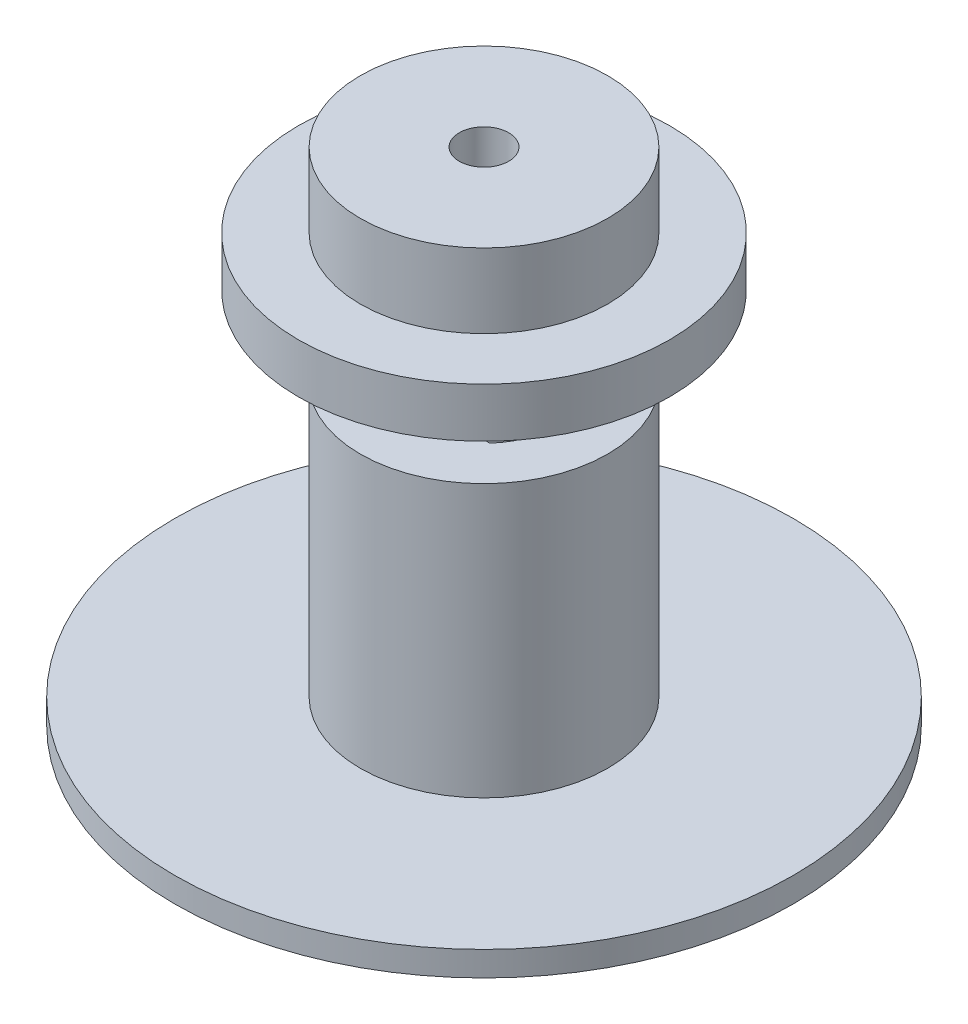
SolidWorks part; units mm, degrees
ref_plane "Front Plane" through (0, 0, 0) normal (0, 0, 1) x (1, 0, 0)
ref_plane "Top Plane" through (0, 0, 0) normal (0, 1, 0) x (1, 0, 0)
ref_plane "Right Plane" through (0, 0, 0) normal (1, 0, 0) x (0, 0, -1)
sketch "Sketch1" plane through (0, 0, 0) normal (0, 1, 0) x (1, 0, 0)
  circle A0 centre (0, 0) radius 10
extrude "Boss-Extrude2" add sketch "Sketch1" along normal blind 1
sketch "Sketch3" plane through (0, 1, 0) normal (0, 1, 0) x (1, 0, 0)
  circle A0 centre (0, 0) radius 5
extrude "Boss-Extrude3" add sketch "Sketch3" along normal blind 14
sketch "Sketch4" plane through (0, 15, 0) normal (0, 1, 0) x (1, 0, 0)
  line L0 (0, 0) -> (0, 2) construction
  line L1 (0, 2) -> (0, -2) construction
  line L3 (0, 2) -> (-4.3147, 2)
  line L4 (0, -2) -> (3.8775, -2)
  line L5 (0, -2) -> (0, 2)
  line L6 (0, 2) -> (3.8775, 2)
  line L7 (3.8775, -2) -> (3.8775, 2)
  line L8 (0, 2) -> (0, -2)
  line L9 (0, -2) -> (-4.3147, -2)
  line L10 (-4.3147, 2) -> (-4.3147, -2)
  circle A0 centre (0, 0) radius 3
extrude "Cut-Extrude1" cut sketch "Sketch4" against normal blind 19 contours L3 A0 L9 L5 | L4 A0 L6 L5 region at (-1.3889, 15, 0) region at (1.3889, 15, 0)
sketch "Sketch5" plane through (0, 1, 0) normal (0, 1, 0) x (1, 0, 0)
  circle A0 centre (0, 0) radius 12.5
extrude "Boss-Extrude4" add sketch "Sketch5" against normal up to surface (1 mm away) up to face at (0, 0, 0)
sketch "Sketch6" plane through (0, 1, 0) normal (0, 1, 0) x (1, 0, 0)
  line L4 (2.2361, 2) -> (-2.2361, 2)
  line L5 (-2.2361, -2) -> (2.2361, -2)
  line L6 (2.2361, 2) -> (-2.2361, 2)
  line L7 (-2.2361, -2) -> (2.2361, -2)
  arc A4 (-2.2361, 2) -> (-2.2361, -2) centre (0, 0) ccw
  arc A5 (2.2361, -2) -> (2.2361, 2) centre (0, 0) ccw
  arc A6 (-2.2361, 2) -> (-2.2361, -2) centre (0, 0) ccw
  arc A7 (2.2361, -2) -> (2.2361, 2) centre (0, 0) ccw
  dimension "D1" = 0
extrude "Cut-Extrude2" cut sketch "Sketch6" against normal blind 19
sketch "Sketch7" plane through (0, 15, 0) normal (0, 1, 0) x (1, 0, 0)
  line L4 (-2.2361, -2) -> (2.2361, -2)
  line L5 (2.2361, 2) -> (-2.2361, 2)
  line L6 (-2.2361, -2) -> (2.2361, -2)
  line L7 (2.2361, 2) -> (-2.2361, 2)
  circle A2 centre (0, 0) radius 5
  circle A3 centre (0, 0) radius 5
  arc A7 (2.2361, -2) -> (2.2361, 2) centre (0, 0) ccw
  arc A8 (-2.2361, 2) -> (-2.2361, -2) centre (0, 0) ccw
  arc A9 (2.2361, -2) -> (2.2361, 2) centre (0, 0) ccw
  arc A10 (-2.2361, 2) -> (-2.2361, -2) centre (0, 0) ccw
  dimension "D1" = 0
  dimension "D2" = 0
extrude "Boss-Extrude5" add sketch "Sketch7" along normal blind 2 separate body contours L6 A9 L7 A10
sketch "Sketch8" plane through (0, 17, 0) normal (0, 1, 0) x (1, 0, 0)
  circle A0 centre (0, 0) radius 7.5
extrude "Boss-Extrude6" add sketch "Sketch8" along normal blind 2
sketch "Sketch9" plane through (0, 19, 0) normal (0, 1, 0) x (1, 0, 0)
  circle A0 centre (0, 0) radius 1
extrude "Cut-Extrude3" cut sketch "Sketch9" against normal blind 25
sketch "Sketch10" plane through (0, 15, 0) normal (0, -1, 0) x (1, 0, 0)
  line L4 (-2.1213, -1.75) -> (2.1213, -1.75)
  line L5 (2.1213, 1.75) -> (-2.1213, 1.75)
  line L6 (-2.1213, -1.75) -> (2.1213, -1.75)
  line L7 (2.1213, 1.75) -> (-2.1213, 1.75)
  arc A4 (-2.1213, 1.75) -> (-2.1213, -1.75) centre (0, 0) ccw
  arc A5 (2.1213, -1.75) -> (2.1213, 1.75) centre (0, 0) ccw
  arc A6 (-2.1213, 1.75) -> (-2.1213, -1.75) centre (0, 0) ccw
  arc A7 (2.1213, -1.75) -> (2.1213, 1.75) centre (0, 0) ccw
  dimension "D1" = 0.25
extrude "Cut-Extrude4" cut sketch "Sketch10" against normal up to surface (2 mm away) up to face at (0, 17, 7.5)
sketch "Sketch11" plane through (0, 17, 0) normal (0, -1, 0) x (1, 0, 0)
  line L4 (-2.1213, -1.75) -> (2.1213, -1.75)
  line L5 (2.1213, 1.75) -> (-2.1213, 1.75)
  line L6 (-2.1213, -1.75) -> (2.1213, -1.75)
  line L7 (2.1213, 1.75) -> (-2.1213, 1.75)
  arc A4 (-2.1213, 1.75) -> (-2.1213, -1.75) centre (0, 0) ccw
  arc A5 (2.1213, -1.75) -> (2.1213, 1.75) centre (0, 0) ccw
  arc A6 (-2.1213, 1.75) -> (-2.1213, -1.75) centre (0, 0) ccw
  arc A7 (2.1213, -1.75) -> (2.1213, 1.75) centre (0, 0) ccw
  dimension "D1" = 0
extrude "Boss-Extrude7" add sketch "Sketch11" along normal blind 10
sketch "Sketch12" plane through (0, 0, 0) normal (0, -1, 0) x (1, 0, 0)
  circle A0 centre (0, 0) radius 4
  circle A3 centre (0, 0) radius 12.5
  circle A4 centre (0, 0) radius 12.5
  dimension "D1" = 0
sketch "Sketch14" plane through (0, 17, 0) normal (0, 1, 0) x (1, 0, 0)
  circle A2 centre (0, 0) radius 1
  circle A3 centre (0, 0) radius 1
  dimension "D1" = 0
extrude "Cut-Extrude5" cut sketch "Sketch14" against normal blind 18
sketch "Sketch15" plane through (0, 7, 0) normal (0, -1, 0) x (1, 0, 0)
  line L4 (-2.1213, -1.75) -> (2.1213, -1.75)
  line L5 (2.1213, 1.75) -> (-2.1213, 1.75)
  line L6 (-2.1213, -1.75) -> (2.1213, -1.75)
  line L7 (2.1213, 1.75) -> (-2.1213, 1.75)
  arc A4 (-2.1213, 1.75) -> (-2.1213, -1.75) centre (0, 0) ccw
  arc A5 (2.1213, -1.75) -> (2.1213, 1.75) centre (0, 0) ccw
  arc A6 (-2.1213, 1.75) -> (-2.1213, -1.75) centre (0, 0) ccw
  arc A7 (2.1213, -1.75) -> (2.1213, 1.75) centre (0, 0) ccw
  circle A8 centre (0, 0) radius 1
  circle A9 centre (0, 0) radius 1
  dimension "D1" = 0
  dimension "D2" = 0
extrude "Boss-Extrude8" add sketch "Sketch15" against normal blind 17
sketch "Sketch16" plane through (0, 7, 0) normal (0, -1, 0) x (1, 0, 0)
  line L4 (-2.1213, -1.75) -> (2.1213, -1.75)
  line L5 (2.1213, 1.75) -> (-2.1213, 1.75)
  line L6 (-2.1213, -1.75) -> (2.1213, -1.75)
  line L7 (2.1213, 1.75) -> (-2.1213, 1.75)
  arc A4 (-2.1213, 1.75) -> (-2.1213, -1.75) centre (0, 0) ccw
  arc A5 (2.1213, -1.75) -> (2.1213, 1.75) centre (0, 0) ccw
  arc A6 (-2.1213, 1.75) -> (-2.1213, -1.75) centre (0, 0) ccw
  arc A7 (2.1213, -1.75) -> (2.1213, 1.75) centre (0, 0) ccw
  circle A8 centre (0, 0) radius 1
  circle A9 centre (0, 0) radius 1
  dimension "D1" = 0
  dimension "D2" = 0
extrude "Cut-Extrude7" cut sketch "Sketch16" against normal up to surface (10 mm away) up to face at (0, 17, 7.5)
sketch "Sketch17" plane through (0, 15, 0) normal (0, -1, 0) x (1, 0, 0)
  line L4 (-2.2361, -2) -> (2.2361, -2)
  line L5 (2.2361, 2) -> (-2.2361, 2)
  line L6 (-2.2361, -2) -> (2.2361, -2)
  line L7 (2.2361, 2) -> (-2.2361, 2)
  arc A4 (-2.2361, 2) -> (-2.2361, -2) centre (0, 0) ccw
  arc A5 (2.2361, -2) -> (2.2361, 2) centre (0, 0) ccw
  arc A6 (-2.2361, 2) -> (-2.2361, -2) centre (0, 0) ccw
  arc A7 (2.2361, -2) -> (2.2361, 2) centre (0, 0) ccw
  dimension "D1" = 0
extrude "Cut-Extrude8" cut sketch "Sketch17" against normal up to surface (2 mm away) up to face at (0, 17, 7.5)
sketch "Sketch18" plane through (0, 17, 0) normal (0, -1, 0) x (1, 0, 0)
  circle A2 centre (0, 0) radius 7.5
  circle A3 centre (0, 0) radius 7.5
  dimension "D1" = 0
extrude "Boss-Extrude9" add sketch "Sketch18" along normal blind 1.75
sketch "Sketch19" plane through (0, 19, 0) normal (0, 1, 0) x (1, 0, 0)
  line L9 (2.1213, 1.75) -> (-2.1213, 1.75)
  line L10 (-2.1213, -1.75) -> (2.1213, -1.75)
  line L11 (2.1213, 1.75) -> (-2.1213, 1.75)
  line L12 (-2.1213, -1.75) -> (2.1213, -1.75)
  circle A0 centre (0, 0) radius 6.5
  circle A2 centre (0, 0) radius 7.5
  circle A3 centre (0, 0) radius 7.5
  arc A11 (-2.1213, 1.75) -> (-2.1213, -1.75) centre (0, 0) ccw
  arc A12 (2.1213, -1.75) -> (2.1213, 1.75) centre (0, 0) ccw
  arc A13 (-2.1213, 1.75) -> (-2.1213, -1.75) centre (0, 0) ccw
  arc A14 (2.1213, -1.75) -> (2.1213, 1.75) centre (0, 0) ccw
  arc M7 (-2.1213, -1.75) -> (-2.1213, 1.75) centre (0, 0) cw
  line M8 (-2.1213, 1.75) -> (2.1213, 1.75)
  arc M9 (2.1213, 1.75) -> (2.1213, -1.75) centre (0, 0) cw
  line M10 (2.1213, -1.75) -> (-2.1213, -1.75)
  circle M11 centre (0, 0) radius 7.5
  dimension "D1" = 0
  dimension "D2" = 1
  dimension "D3" = 0
extrude "Cut-Extrude9" cut sketch "Sketch19" against normal blind 1.75 contours A0 M11 | A0 M10 M7 M8 M9 region at (-6.3162, 19, 0) region at (-7.2879, 19, 0)
sketch "Sketch20" plane through (0, 15, 0) normal (0, 1, 0) x (1, 0, 0)
  circle A2 centre (0, 0) radius 5
  circle A3 centre (0, 0) radius 5
  dimension "D1" = 0
extrude "Cut-Extrude10" cut sketch "Sketch20" against normal blind 3
sketch "Sketch21" plane through (0, 17.25, 0) normal (0, 1, 0) x (1, 0, 0)
  circle A2 centre (0, 0) radius 7.5
  circle A3 centre (0, 0) radius 7.5
  circle A4 centre (0, 0) radius 5
  circle A5 centre (0, 0) radius 1
  circle A6 centre (0, 0) radius 1
  line M5 (2.1213, -1.75) -> (-2.1213, -1.75)
  arc M6 (-2.1213, -1.75) -> (-2.1213, 1.75) centre (0, 0) cw
  line M7 (-2.1213, 1.75) -> (2.1213, 1.75)
  arc M8 (2.1213, 1.75) -> (2.1213, -1.75) centre (0, 0) cw
  dimension "D1" = 0
  dimension "D2" = 0
extrude "Boss-Extrude10" add sketch "Sketch21" along normal blind 3 contours A4 M8 M5 M6 M7 region at (-4.8586, 17.25, 0)
sketch "Sketch22" plane through (0, 24, 0) normal (0, 1, 0) x (1, 0, 0)
  line L4 (-2.1213, -1.75) -> (2.1213, -1.75)
  line L5 (2.1213, 1.75) -> (-2.1213, 1.75)
  line L6 (-2.1213, -1.75) -> (2.1213, -1.75)
  line L7 (2.1213, 1.75) -> (-2.1213, 1.75)
  arc A4 (-2.1213, 1.75) -> (-2.1213, -1.75) centre (0, 0) ccw
  arc A5 (2.1213, -1.75) -> (2.1213, 1.75) centre (0, 0) ccw
  arc A6 (-2.1213, 1.75) -> (-2.1213, -1.75) centre (0, 0) ccw
  arc A7 (2.1213, -1.75) -> (2.1213, 1.75) centre (0, 0) ccw
  dimension "D1" = 0
extrude "Cut-Extrude11" cut sketch "Sketch22" against normal up to surface (3.75 mm away) up to face at (0, 20.25, 0)
sketch "Sketch23" plane through (0, 17, 0) normal (0, 1, 0) x (1, 0, 0)
  circle A2 centre (0, 0) radius 1
  circle A3 centre (0, 0) radius 1
  dimension "D1" = 0
extrude "Cut-Extrude13" cut sketch "Sketch23" against normal up to surface (1.75 mm away) up to face at (0, 15.25, -7.5)
sketch "Sketch24" plane through (0, 1, 0) normal (0, 1, 0) x (1, 0, 0)
  circle A2 centre (0, 0) radius 12.5
  circle A3 centre (0, 0) radius 12.5
  circle A4 centre (0, 0) radius 7.5 construction
  circle A5 centre (0, 0) radius 5
  circle A6 centre (0, 0) radius 5
  dimension "D1" = 0
  dimension "D2" = 4
sketch "Sketch25" plane through (0, 15.25, 0) normal (0, -1, 0) x (1, 0, 0)
  circle A6 centre (0, 0) radius 4
  circle A7 centre (0, 0) radius 4
  dimension "D2" = 3
extrude "Cut-Extrude15" cut sketch "Sketch25" against normal blind 3
